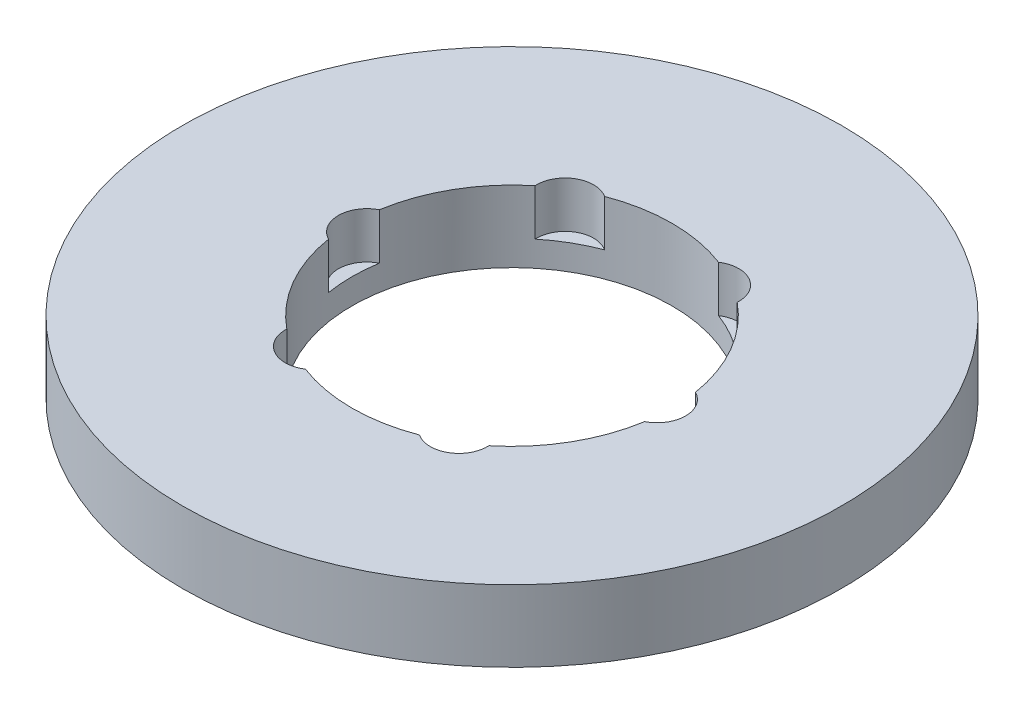
SolidWorks part; units mm, degrees
ref_plane "Front Plane" through (0, 0, 0) normal (0, 0, 1) x (1, 0, 0)
ref_plane "Top Plane" through (0, 0, 0) normal (0, 1, 0) x (1, 0, 0)
ref_plane "Right Plane" through (0, 0, 0) normal (1, 0, 0) x (0, 0, -1)
sketch "Sketch1" plane through (0, 0, 0) normal (0, 1, 0) x (1, 0, 0)
  circle A0 centre (0, 0) radius 87.5
  dimension "FLANGE_OD" = 175
extrude "Boss-Extrude1" add sketch "Sketch1" along normal blind 19
sketch "Sketch2" plane through (0, 0, 0) normal (0, 1, 0) x (1, 0, 0)
  circle A0 centre (0, 0) radius 42.5
  dimension "BORE_D" = 85
extrude "Cut-Extrude1" cut sketch "Sketch2" along normal through all
sketch "Sketch3" plane through (0, 19, 0) normal (0, 1, 0) x (1, 0, 0)
  circle A0 centre (0, 0) radius 38.5323 construction
  circle A1 centre (-38.5323, 0) radius 7.571
  dimension "BOLT_D" = 15.1421
  dimension "BOLT_PCD" = 77.0645
extrude "Cut-Extrude2" cut sketch "Sketch3" against normal blind 12.2812
pattern_circular "CirPattern1" count 6 over 360 about axis through (0, 0, 0) along (0, 1, 0) of "Cut-Extrude2"
